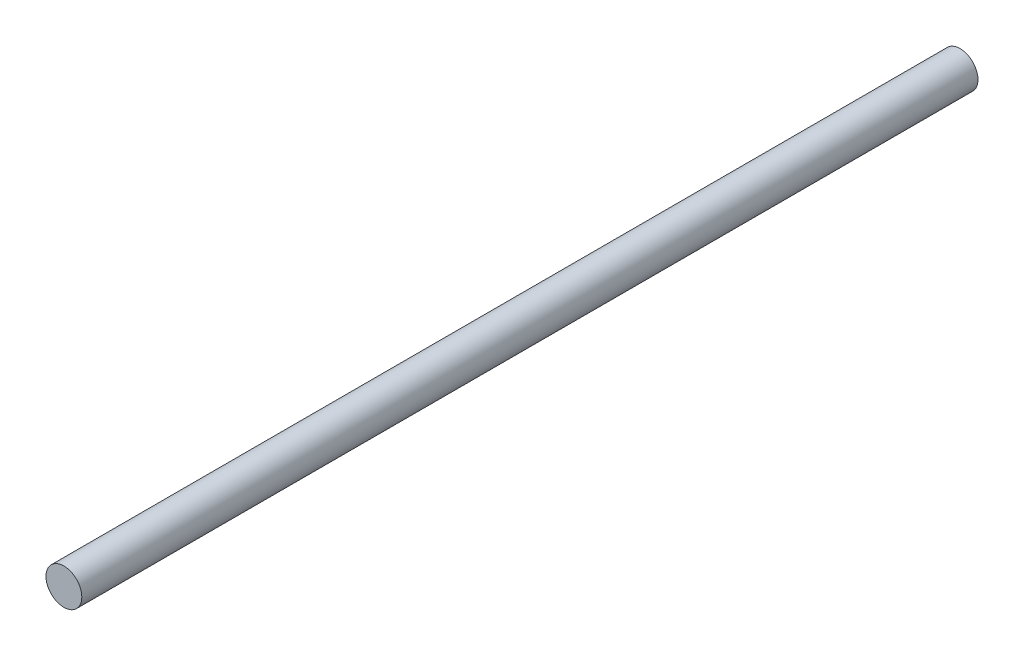
SolidWorks part; units mm, degrees
ref_plane "前视基准面" through (0, 0, 0) normal (0, 0, 1) x (1, 0, 0)
ref_plane "上视基准面" through (0, 0, 0) normal (0, 1, 0) x (1, 0, 0)
ref_plane "右视基准面" through (0, 0, 0) normal (1, 0, 0) x (0, 0, -1)
other "Configuration Table"
sketch "草图1" plane through (0, 0, 0) normal (0, 0, 1) x (1, 0, 0)
  circle A0 centre (0, 0) radius 6
  dimension "D1" = 12
extrude "凸台-拉伸1" add sketch "草图1" along normal blind 300
